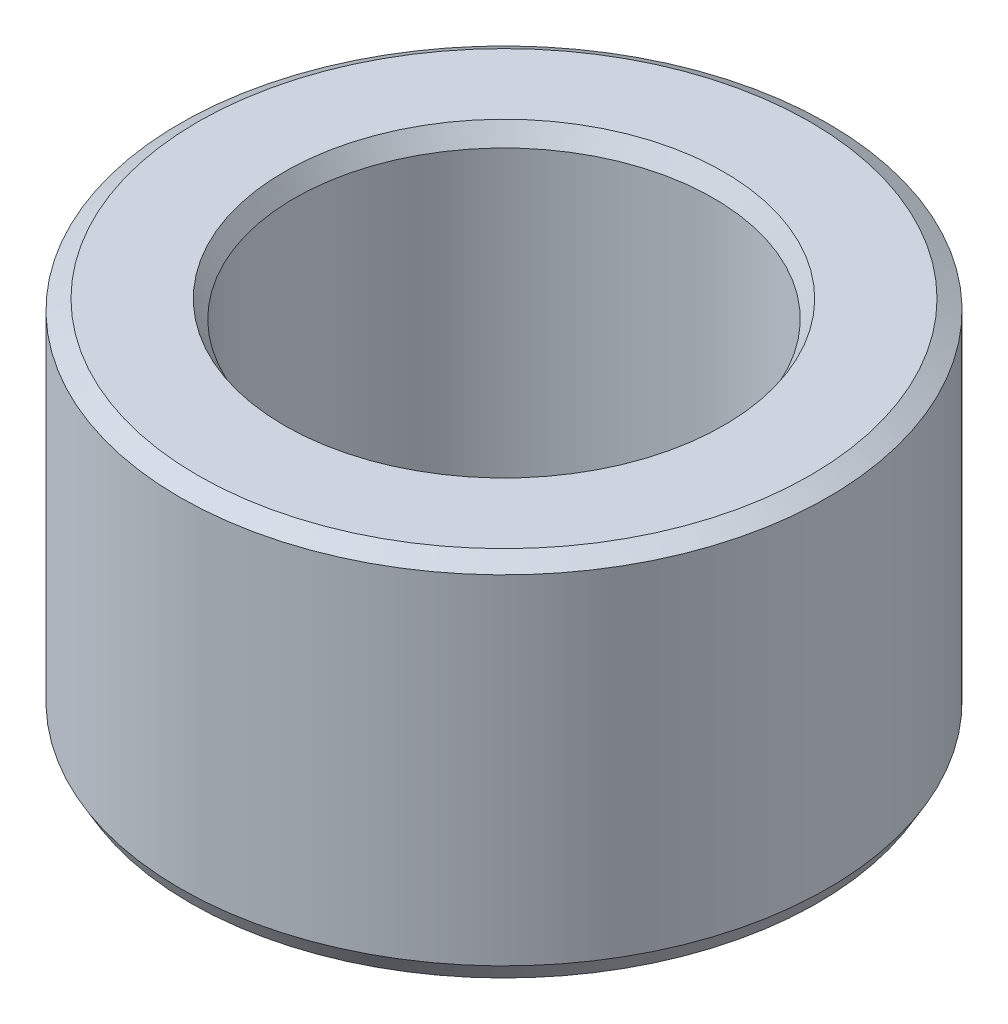
SolidWorks part; units mm, degrees
ref_plane "Front Plane" through (0, 0, 0) normal (0, 0, 1) x (1, 0, 0)
ref_plane "Top Plane" through (0, 0, 0) normal (0, 1, 0) x (1, 0, 0)
ref_plane "Right Plane" through (0, 0, 0) normal (1, 0, 0) x (0, 0, -1)
sketch "Sketch1" plane through (0, 0, 0) normal (0, 1, 0) x (1, 0, 0)
  circle A0 centre (0, 0) radius 50
  dimension "SLEEVE_OD" = 100
extrude "Boss-Extrude1" add sketch "Sketch1" along normal blind 56.5848
sketch "Sketch2" plane through (0, 0, 0) normal (0, 1, 0) x (1, 0, 0)
  circle A0 centre (0, 0) radius 32.3406
  dimension "BORE_D" = 64.6812
extrude "Cut-Extrude1" cut sketch "Sketch2" along normal through all
chamfer "Chamfer1" distance 1.5767 angle 60 4 edges at (0, 56.5848, 32.3406) (0, 0, 32.3406) (0, 0, 50) (0, 56.5848, 50) first distance on face at (0, 56.5848, 32.3406) first distance on face at (0, 0, 32.3406) first distance on face at (0, 56.5848, 50)
